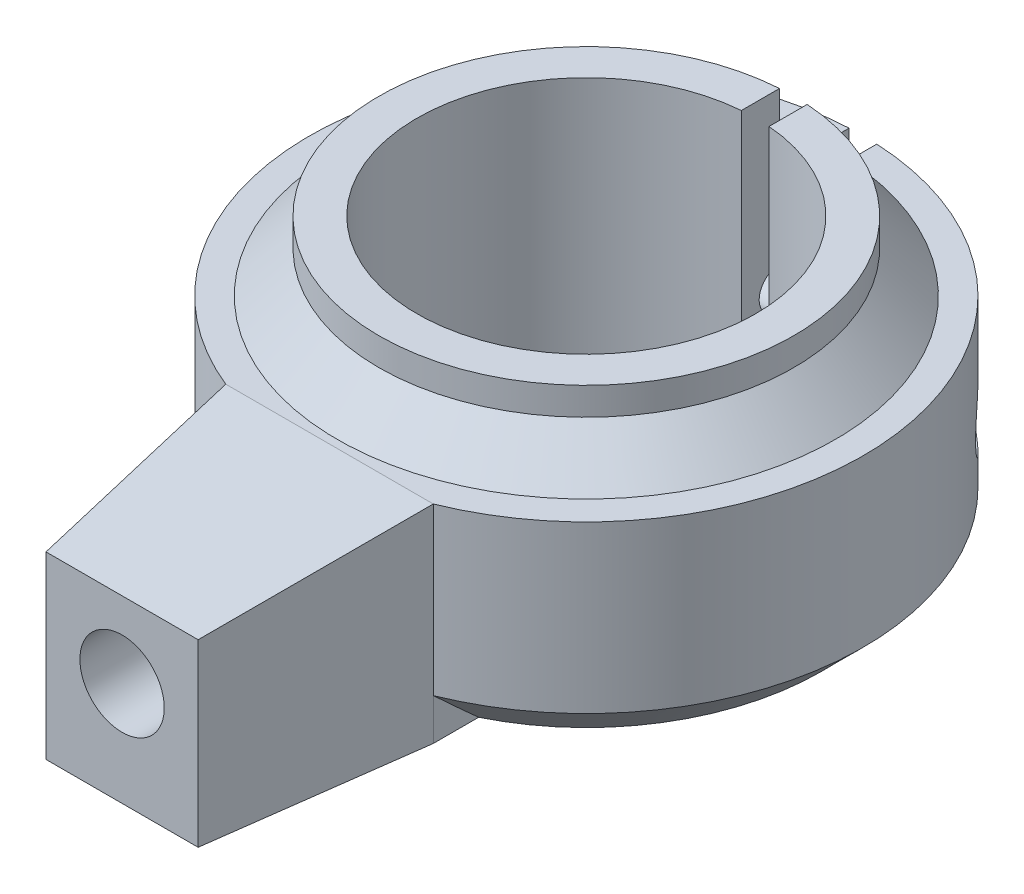
SolidWorks part; units mm, degrees
ref_plane "Front Plane" through (0, 0, 0) normal (0, 0, 1) x (1, 0, 0)
ref_plane "Top Plane" through (0, 0, 0) normal (0, 1, 0) x (1, 0, 0)
ref_plane "Right Plane" through (0, 0, 0) normal (1, 0, 0) x (0, 0, -1)
sketch "Sketch1" plane through (0, 0, 0) normal (0, 1, 0) x (1, 0, 0)
  line L0 (-16.7192, 14.6196) -> (-16.7192, 22.4105)
  line L2 (-23.2192, -16.1569) -> (-8.2192, -16.1569)
  line L3 (-23.2192, -16.1569) -> (-23.2192, -31.1569)
  line L4 (-23.2192, -31.1569) -> (-8.2192, -31.1569)
  line L5 (-8.2192, -16.1569) -> (-8.2192, -31.1569)
  line L9 (-16.7192, 22.4105) -> (-14.7192, 22.4105)
  line L10 (-14.7192, 22.4105) -> (-14.7192, 14.6196)
  circle A0 centre (-15.7192, 2.4105) radius 12.25
  circle A1 centre (-15.7192, 2.4105) radius 20.025
  dimension "D1" = 24.5
  dimension "D4" = 40.05
  dimension "D2" = 15
  dimension "D3" = 15
  dimension "D8" = 2
  dimension "D9" = 1
extrude "Boss-Extrude1" add sketch "Sketch1" along normal blind 15 contours A0 L0 L3 L10 | L3 L4 L5 L2 region at (-24.3969, 0, 7.0071)
sketch "Sketch2" plane through (0, 0, 31.1569) normal (0, 0, 1) x (1, 0, 0)
  circle A0 centre (-15.7192, 7.5) radius 3.05
  dimension "D1" = 6.1
extrude "Cut-Extrude1" cut sketch "Sketch2" against normal blind 15
sketch "Sketch3" plane through (0, 15, 0) normal (0, 1, 0) x (1, 0, 0)
  line L0 (-16.7192, 17.3771) -> (-16.7192, 14.6196)
  line L1 (-14.7192, 14.6196) -> (-14.7192, 17.3771)
  line L2 (-14.7192, 22.4105) -> (-14.7192, 14.6196) construction
  line L3 (-16.7192, 14.6196) -> (-16.7192, 22.4105) construction
  circle A0 centre (-15.7192, 2.4105) radius 15
  circle A1 centre (-15.7192, 2.4105) radius 12.25
  line M4 (-14.7192, 22.4105) -> (-14.7192, 14.6196)
  arc M5 (-14.7192, 14.6196) -> (-16.7192, 14.6196) centre (-15.7192, 2.4105) cw
  line M6 (-16.7192, 14.6196) -> (-16.7192, 22.4105)
  dimension "D1" = 30
extrude "Boss-Extrude2" add sketch "Sketch3" along normal blind 5 contours A0 M6 M4 M5 region at (-17.1432, 15, -15.9984)
chamfer "Chamfer4" distance 3 angle 45 3 edges at (-15.7192, 15, 12.5895) (4.0273, 0, -5.7385) (-35.4657, 0, -5.7385)
chamfer "Chamfer6" distance 15 distance2 2 3 edges at (-8.2192, 7.5, 31.1569) (-15.7192, 15, 31.1569) (-23.2192, 7.5, 31.1569) first distance on face at (-8.2192, 6.3, 21.1719) first distance on face at (-15.7192, 15, 4.9738) first distance on face at (-23.2192, 6.9, 21.8286)
sketch "Sketch4" plane through (-14.7192, 0, 0) normal (-1, 0, 0) x (0, 0, 1)
  line L0 (-19.4061, 0) -> (-14.6196, 0) construction
  line L2 (-22.4105, 15) -> (-22.4105, 3) construction
  circle A0 centre (-17.4105, 7.5) radius 1.5
  dimension "D1" = 3
  dimension "D2" = 7.5
  dimension "D3" = 5
extrude "Cut-Extrude2" cut sketch "Sketch4" against normal blind 25 and the other way blind 29
ref_plane "Plane1" through (4.3058, 0, 0) normal (1, 0, 0) x (0, 0, -1)
sketch "Sketch5" plane through (4.3058, 0, 0) normal (1, 0, 0) x (0, 0, -1)
  circle A0 centre (17.4105, 7.5) radius 2.5
  dimension "D1" = 5
extrude "Cut-Extrude3" cut sketch "Sketch5" against normal offset from surface (14.025 mm away) 5 up to face at (-14.7192, 7.5, -18.9105)
ref_plane "Plane2" through (-35.7442, 0, 0) normal (-1, 0, 0) x (0, 0, 1)
sketch "Sketch6" plane through (-35.7442, 0, 0) normal (-1, 0, 0) x (0, 0, 1)
  circle A0 centre (-17.4105, 7.5) radius 2.5
  dimension "D1" = 5
extrude "Cut-Extrude4" cut sketch "Sketch6" against normal offset from surface (14.025 mm away) 5 up to face at (-16.7192, 7.5, -15.9105)
